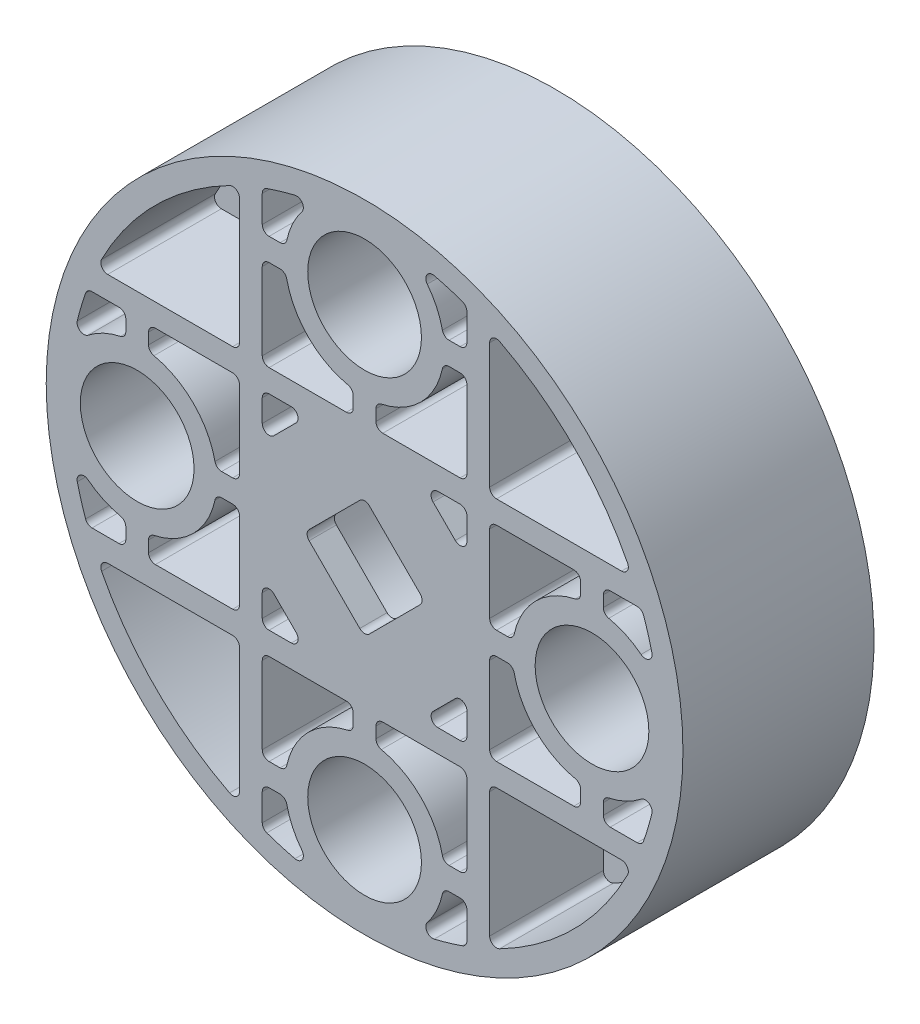
SolidWorks part; units mm, degrees
ref_plane "Front Plane" through (0, 0, 0) normal (0, 0, 1) x (1, 0, 0)
ref_plane "Top Plane" through (0, 0, 0) normal (0, 1, 0) x (1, 0, 0)
ref_plane "Right Plane" through (0, 0, 0) normal (1, 0, 0) x (0, 0, -1)
sketch "Sketch1" plane through (0, 0, 0) normal (0, 0, 1) x (1, 0, 0)
  line L0 (-22.0244, -11.2) -> (5.9756, -11.2) construction
  line L1 (-8.0244, -25.2) -> (-8.0244, 2.8) construction
  circle A0 centre (-8.0244, -11.2) radius 14 construction
  circle A1 centre (-8.0244, -11.2) radius 14
  circle A2 centre (-18.0244, -11.2) radius 2.5 construction
  circle A3 centre (-18.0244, -11.2) radius 2.5
  circle A4 centre (-8.0244, -1.2) radius 2.5 construction
  circle A5 centre (-8.0244, -1.2) radius 2.5
  circle A8 centre (-8.0244, -21.2) radius 2.5 construction
  circle A9 centre (1.9756, -11.2) radius 2.5 construction
  circle A10 centre (-8.0244, -21.2) radius 2.5
  circle A11 centre (1.9756, -11.2) radius 2.5
extrude "Boss-Extrude1" add sketch "Sketch1" along normal up to vertex (9.2 mm away)
sketch "Sketch2" plane through (0, 0, 9.2) normal (0, 0, 1) x (1, 0, 0)
  line L0 (-9.9744, -12.9197) -> (-9.9744, -9.4803)
  line L2 (-6.0744, -12.9197) -> (-6.0744, -9.4803)
  circle A0 centre (-8.0244, -11.2) radius 2.6
  dimension "D1" = 5.2
  dimension "D2" = 3.9
extrude "Cut-Extrude1" cut sketch "Sketch2" against normal through all contours L2 A0 L0
sketch "Sketch3" plane through (0, 0, 9.2) normal (0, 0, 1) x (1, 0, 0)
  line L0 (-12.5244, -23.2) -> (-12.5244, -23.3963)
  line L1 (-20.0244, -6.7) -> (-20.2207, -6.7)
  line L2 (-13.0244, 0.8) -> (-13.0244, -23.2) construction
  line L3 (-3.0244, -23.2) -> (-3.0244, 0.8) construction
  line L4 (-4.0744, -13.5574) -> (-4.0744, -8.8426)
  line L5 (-11.9744, -8.8426) -> (-11.9744, -13.5574)
  line L6 (-4.0744, -13.5574) -> (-4.0744, -8.8426)
  line L7 (-11.9744, -8.8426) -> (-11.9744, -13.5574)
  line L8 (-8.0244, -11.2) -> (-8.0244, 2.8) construction
  line L9 (-13.5244, 0.5792) -> (-13.5244, -22.9792)
  line L10 (-12.5244, 0.9963) -> (-12.5244, -23.2)
  line L11 (-2.5244, -22.9792) -> (-2.5244, 0.5792)
  line L12 (-3.5244, -23.3963) -> (-3.5244, 0.9963)
  line L13 (-3.5244, -23.2) -> (-3.5244, 0.8) construction
  line L14 (-2.5244, -23.2) -> (-2.5244, 0.8) construction
  line L15 (-12.5244, 0.8) -> (-12.5244, -23.2) construction
  line L16 (-13.5244, 0.8) -> (-13.5244, -23.2) construction
  line L17 (4.1719, -6.7) -> (-20.0244, -6.7)
  line L18 (3.7548, -5.7) -> (-19.8036, -5.7)
  line L19 (-20.2207, -15.7) -> (4.1719, -15.7)
  line L20 (-19.8036, -16.7) -> (3.7548, -16.7)
  line L21 (-8.0244, -11.2) -> (-12.5244, -23.2) construction
  line L22 (-8.0244, -11.2) -> (-20.0244, -6.7) construction
  circle A2 centre (-18.0244, -11.2) radius 3.5
  circle A3 centre (-18.0244, -11.2) radius 3.5
  circle A19 centre (-8.0244, -21.2) radius 3.5
  circle A20 centre (-8.0244, -21.2) radius 3.5
  circle A22 centre (1.9756, -11.2) radius 3.5
  circle A23 centre (1.9756, -11.2) radius 3.5
  circle A25 centre (-8.0244, -1.2) radius 3.5
  circle A26 centre (-8.0244, -1.2) radius 3.5
  circle A28 centre (-8.0244, -11.2) radius 13
  circle A29 centre (-8.0244, -11.2) radius 13
  arc A34 (-11.9744, -13.5574) -> (-4.0744, -13.5574) centre (-8.0244, -11.2) ccw
  arc A35 (-4.0744, -8.8426) -> (-11.9744, -8.8426) centre (-8.0244, -11.2) ccw
  arc A36 (-11.9744, -13.5574) -> (-4.0744, -13.5574) centre (-8.0244, -11.2) ccw
  arc A37 (-4.0744, -8.8426) -> (-11.9744, -8.8426) centre (-8.0244, -11.2) ccw
  dimension "D7" = 5
  dimension "D8" = 5
  dimension "D13" = 2
  dimension "D14" = 90
  dimension "D1" = 1
  dimension "D2" = 1
  dimension "D3" = 1
  dimension "D4" = 1
  dimension "D5" = 1
  dimension "D6" = 2
  dimension "D9" = 0.5
  dimension "D10" = 0.5
  dimension "D11" = 0.5
  dimension "D12" = 0.5
extrude "Cut-Extrude2" cut sketch "Sketch3" against normal blind 5 contours L9 A29 L18 | L12 A29 A26 L10 L18 | L1 A29 A3 L19 L9 L17 | A37 L17 L10 L19 A36 L7 | A37 L6 A36 L19 L12 L17 | A23 A29 L17 L11 L19 | L18 A29 L11 | L11 A29 L20 | L0 A29 A20 L12 L20 L10 | L20 A29 L9
sketch "Sketch4" plane through (0, 0, 0) normal (0, 0, -1) x (-1, 0, 0)
  circle A2 centre (8.0244, -11.2) radius 13
  circle A3 centre (8.0244, -11.2) radius 13
  dimension "D1" = 1
extrude "Cut-Extrude3" cut sketch "Sketch4" against normal blind 0.8
sketch "Sketch5" plane through (0, 0, 0.8) normal (0, 0, -1) x (-1, 0, 0)
  line L0 (8.0244, 2.8) -> (8.0244, -25.2) construction
  circle A0 centre (8.0244, -11.2) radius 4.25
  dimension "D1" = 8.5
extrude "Cut-Extrude4" cut sketch "Sketch5" against normal offset from surface (0.7 mm away) 1.5 up to face at (-21.0244, -11.2, 0)
sketch "Sketch6" plane through (0, 0, 0.8) normal (0, 0, -1) x (-1, 0, 0)
  circle A0 centre (8.0244, -11.2) radius 4.25 construction
  circle A1 centre (8.0244, -11.2) radius 4.25
  circle A2 centre (8.0244, -11.2) radius 5.25
  dimension "D1" = 1
extrude "Boss-Extrude2" add sketch "Sketch6" along normal up to surface (0.8 mm away) up to face at (-21.0244, -11.2, 0)
sketch "Sketch7" plane through (0, 0, 0.8) normal (0, 0, -1) x (-1, 0, 0)
  line L0 (7.0705, -15.7) -> (3.5244, -15.7) construction
  line L1 (3.5244, -6.7) -> (7.0705, -6.7) construction
  line L2 (3.5244, -5.7) -> (12.5244, -5.7) construction
  line L3 (12.5244, -16.7) -> (3.5244, -16.7) construction
  line L4 (-3.7548, -5.7) -> (2.5244, -5.7) construction
  line L5 (-4.1719, -6.7) -> (2.5244, -6.7) construction
  line L6 (2.5244, -15.7) -> (-4.1719, -15.7) construction
  line L7 (2.5244, -16.7) -> (-3.7548, -16.7) construction
  line L8 (2.5244, -22.9792) -> (2.5244, -16.7) construction
  line L9 (3.5244, -23.3963) -> (3.5244, -16.7) construction
  line L10 (2.5244, -15.7) -> (2.5244, -6.7) construction
  line L11 (2.5244, -5.7) -> (2.5244, 0.5792) construction
  line L12 (3.5244, -5.7) -> (3.5244, 0.9963) construction
  line L13 (3.5244, -15.7) -> (3.5244, -6.7) construction
  line L14 (12.5244, -16.7) -> (12.5244, -23.3963) construction
  line L15 (12.5244, 0.9963) -> (12.5244, -5.7) construction
  line L16 (12.5244, -6.7) -> (12.5244, -15.7) construction
  line L17 (13.5244, -16.7) -> (13.5244, -22.9792) construction
  line L18 (13.5244, 0.5792) -> (13.5244, -5.7) construction
  line L19 (13.5244, -5.7) -> (19.8036, -5.7) construction
  line L20 (13.5244, -6.7) -> (20.2207, -6.7) construction
  line L21 (13.5244, -6.7) -> (13.5244, -15.7) construction
  line L22 (20.2207, -15.7) -> (13.5244, -15.7) construction
  line L23 (19.8036, -16.7) -> (13.5244, -16.7) construction
  line L24 (12.5244, -15.7) -> (3.5244, -15.7)
  line L25 (3.5244, -6.7) -> (12.5244, -6.7)
  line L26 (3.5244, -5.7) -> (12.5244, -5.7)
  line L27 (12.5244, -16.7) -> (3.5244, -16.7)
  line L28 (-3.7548, -5.7) -> (2.5244, -5.7)
  line L29 (-4.1719, -6.7) -> (2.5244, -6.7)
  line L30 (2.5244, -15.7) -> (-4.1719, -15.7)
  line L31 (2.5244, -16.7) -> (-3.7548, -16.7)
  line L32 (2.5244, -22.9792) -> (2.5244, -16.7)
  line L33 (3.5244, -23.3963) -> (3.5244, -16.7)
  line L34 (2.5244, -15.7) -> (2.5244, -6.7)
  line L35 (2.5244, -5.7) -> (2.5244, 0.5792)
  line L36 (3.5244, -5.7) -> (3.5244, 0.9963)
  line L37 (3.5244, -15.7) -> (3.5244, -6.7)
  line L38 (12.5244, -16.7) -> (12.5244, -23.3963)
  line L39 (12.5244, 0.9963) -> (12.5244, -5.7)
  line L40 (12.5244, -6.7) -> (12.5244, -15.7)
  line L41 (13.5244, -16.7) -> (13.5244, -22.9792)
  line L42 (13.5244, 0.5792) -> (13.5244, -5.7)
  line L43 (13.5244, -5.7) -> (19.8036, -5.7)
  line L44 (13.5244, -6.7) -> (20.2207, -6.7)
  line L45 (13.5244, -6.7) -> (13.5244, -15.7)
  line L46 (20.2207, -15.7) -> (13.5244, -15.7)
  line L47 (19.8036, -16.7) -> (13.5244, -16.7)
  circle A2 centre (18.0244, -11.2) radius 3.5
  circle A3 centre (18.0244, -11.2) radius 3.5
  circle A5 centre (8.0244, -1.2) radius 3.5
  circle A6 centre (8.0244, -1.2) radius 3.5
  circle A8 centre (-1.9756, -11.2) radius 3.5
  circle A9 centre (-1.9756, -11.2) radius 3.5
  circle A10 centre (8.0244, -11.2) radius 13 construction
  circle A11 centre (8.0244, -21.2) radius 3.5
  circle A12 centre (8.0244, -21.2) radius 3.5
  circle A13 centre (8.0244, -11.2) radius 13
  circle A14 centre (8.0244, -11.2) radius 5.25 construction
  circle A15 centre (8.0244, -11.2) radius 5.25
  circle A17 centre (8.0244, -11.2) radius 14
  circle A18 centre (8.0244, -11.2) radius 14
  circle M6 centre (8.0244, -11.2) radius 13
  circle M11 centre (8.0244, -11.2) radius 5.25
  dimension "D1" = 1
  dimension "D2" = 1
  dimension "D3" = 1
  dimension "D4" = 1
  dimension "D5" = 0
extrude "Cut-Extrude5" cut sketch "Sketch7" against normal offset from surface (2.4 mm away) 1 contours L28 L35 M6 | A9 L30 L34 L29 M6 | L32 L31 M6 | A12 L38 L27 L33 M6 | A6 L36 L26 L39 M6 | L42 L43 M6 | A3 L44 L45 L46 M6 | L47 L41 M6 | L40 L24 M11 | L40 L25 M11 | L37 L25 M11 | L37 L24 M11 up to face at (-0.2471, -18.9773, 4.2)
chamfer "Chamfer1" distance 0.6 angle 45 4 edges at (-6.0744, -11.2, 1.5) (-8.0244, -8.6, 1.5) (-8.0244, -13.8, 1.5) (-9.9744, -11.2, 1.5)
sketch "Sketch8" plane through (0, 0, 9.2) normal (0, 0, 1) x (1, 0, 0)
  line L0 (-11.9744, -8.8426) -> (-11.9744, -13.5574) construction
  line L1 (-11.9744, -8.8426) -> (-11.9744, -13.5574)
  line L2 (-4.0744, -13.5574) -> (-4.0744, -8.8426) construction
  line L3 (-4.0744, -13.5574) -> (-4.0744, -8.8426)
  line L4 (-8.0244, -7.1341) -> (-12.0903, -11.2)
  line L5 (-3.9586, -11.2) -> (-8.0244, -7.1341)
  line L6 (-8.0244, -15.2659) -> (-3.9586, -11.2)
  line L7 (-12.0903, -11.2) -> (-8.0244, -15.2659)
  line L8 (-8.0244, -7.1341) -> (-12.0903, -11.2)
  line L9 (-3.9586, -11.2) -> (-8.0244, -7.1341)
  line L10 (-8.0244, -15.2659) -> (-3.9586, -11.2)
  line L11 (-12.0903, -11.2) -> (-8.0244, -15.2659)
  line L12 (-8.0244, -13.8517) -> (-5.3728, -11.2)
  line L13 (-10.6761, -11.2) -> (-8.0244, -13.8517)
  line L14 (-8.0244, -8.5483) -> (-10.6761, -11.2)
  line L15 (-5.3728, -11.2) -> (-8.0244, -8.5483)
  line L16 (-8.0244, -13.8517) -> (-5.3728, -11.2)
  line L17 (-10.6761, -11.2) -> (-8.0244, -13.8517)
  line L18 (-8.0244, -8.5483) -> (-10.6761, -11.2)
  line L19 (-5.3728, -11.2) -> (-8.0244, -8.5483)
  line L20 (-3.5244, -6.7) -> (-12.5244, -6.7)
  line L21 (-3.5244, -15.7) -> (-3.5244, -6.7)
  line L22 (-12.5244, -15.7) -> (-3.5244, -15.7)
  line L23 (-12.5244, -6.7) -> (-12.5244, -15.7)
  line L24 (-3.5244, -6.7) -> (-12.5244, -6.7)
  line L25 (-3.5244, -15.7) -> (-3.5244, -6.7)
  line L26 (-12.5244, -15.7) -> (-3.5244, -15.7)
  line L27 (-12.5244, -6.7) -> (-12.5244, -15.7)
  dimension "D1" = 0
  dimension "D2" = 0
  dimension "D3" = 0
extrude "Cut-Extrude6" cut sketch "Sketch8" against normal up to surface (5 mm away)
sketch "Sketch9" plane through (0, 0, 9.2) normal (0, 0, 1) x (1, 0, 0)
  line L0 (-4.0744, -13.5574) -> (-4.0744, -8.8426) construction
  line L1 (-11.9744, -8.8426) -> (-11.9744, -13.5574) construction
  line L2 (-4.0744, -13.5574) -> (-4.0744, -8.8426)
  line L3 (-11.9744, -8.8426) -> (-11.9744, -13.5574)
  line L4 (-3.5244, -6.7) -> (-12.5244, -6.7)
  line L5 (-12.5244, -6.7) -> (-12.5244, -15.7)
  line L6 (-12.5244, -15.7) -> (-3.5244, -15.7)
  line L7 (-3.5244, -15.7) -> (-3.5244, -6.7)
  line L8 (-3.5244, -6.7) -> (-12.5244, -6.7)
  line L9 (-12.5244, -6.7) -> (-12.5244, -15.7)
  line L10 (-12.5244, -15.7) -> (-3.5244, -15.7)
  line L11 (-3.5244, -15.7) -> (-3.5244, -6.7)
  line L12 (-8.0244, -13.8517) -> (-5.3728, -11.2)
  line L13 (-5.3728, -11.2) -> (-8.0244, -8.5483)
  line L14 (-8.0244, -8.5483) -> (-10.6761, -11.2)
  line L15 (-10.6761, -11.2) -> (-8.0244, -13.8517)
  line L16 (-8.0244, -13.8517) -> (-5.3728, -11.2)
  line L17 (-5.3728, -11.2) -> (-8.0244, -8.5483)
  line L18 (-8.0244, -8.5483) -> (-10.6761, -11.2)
  line L19 (-10.6761, -11.2) -> (-8.0244, -13.8517)
  line L20 (-8.0244, -7.1341) -> (-12.0903, -11.2)
  line L21 (-12.0903, -11.2) -> (-8.0244, -15.2659)
  line L22 (-8.0244, -15.2659) -> (-3.9586, -11.2)
  line L23 (-3.9586, -11.2) -> (-8.0244, -7.1341)
  line L24 (-8.0244, -7.1341) -> (-12.0903, -11.2)
  line L25 (-12.0903, -11.2) -> (-8.0244, -15.2659)
  line L26 (-8.0244, -15.2659) -> (-3.9586, -11.2)
  line L27 (-3.9586, -11.2) -> (-8.0244, -7.1341)
  line M18 (-11.9744, -11.0841) -> (-11.9744, -11.3159)
  line M21 (-4.0744, -11.3159) -> (-4.0744, -11.0841)
  dimension "D1" = 0
  dimension "D2" = 0
  dimension "D3" = 0
extrude "Boss-Extrude3" add sketch "Sketch9" against normal up to surface (5 mm away) contours L24 L25 M18 | L26 L27 M21 up to face at (-8.0244, -11.2, 4.2)
sketch "Sketch10" plane through (0, 0, 9.2) normal (0, 0, 1) x (1, 0, 0)
  line L4 (-8.0244, -7.1341) -> (-12.0903, -11.2)
  line L5 (-12.0903, -11.2) -> (-8.0244, -15.2659)
  line L6 (-8.0244, -15.2659) -> (-3.9586, -11.2)
  line L7 (-3.9586, -11.2) -> (-8.0244, -7.1341)
  line L8 (-8.0244, -7.1341) -> (-12.0903, -11.2)
  line L9 (-12.0903, -11.2) -> (-8.0244, -15.2659)
  line L10 (-8.0244, -15.2659) -> (-3.9586, -11.2)
  line L11 (-3.9586, -11.2) -> (-8.0244, -7.1341)
  dimension "D1" = 0
extrude "Boss-Extrude4" add sketch "Sketch10" against normal up to surface (0.2 mm away)
sketch "Sketch11" plane through (0, 0, 9.2) normal (0, 0, 1) x (1, 0, 0)
  line L0 (-11.9744, -8.8426) -> (-11.9744, -13.5574) construction
  line L1 (-4.0744, -13.5574) -> (-4.0744, -8.8426) construction
  line L2 (-11.9744, -8.8426) -> (-11.9744, -13.5574)
  line L3 (-4.0744, -13.5574) -> (-4.0744, -8.8426)
  line L4 (-8.0244, -7.1341) -> (-12.0903, -11.2)
  line L5 (-12.0903, -11.2) -> (-8.0244, -15.2659)
  line L6 (-8.0244, -15.2659) -> (-3.9586, -11.2)
  line L7 (-3.9586, -11.2) -> (-8.0244, -7.1341)
  line L8 (-8.0244, -7.1341) -> (-12.0903, -11.2)
  line L9 (-12.0903, -11.2) -> (-8.0244, -15.2659)
  line L10 (-8.0244, -15.2659) -> (-3.9586, -11.2)
  line L11 (-3.9586, -11.2) -> (-8.0244, -7.1341)
  line L12 (-8.0244, -13.8517) -> (-5.3728, -11.2)
  line L13 (-5.3728, -11.2) -> (-8.0244, -8.5483)
  line L14 (-8.0244, -8.5483) -> (-10.6761, -11.2)
  line L15 (-10.6761, -11.2) -> (-8.0244, -13.8517)
  line L16 (-8.0244, -13.8517) -> (-5.3728, -11.2)
  line L17 (-5.3728, -11.2) -> (-8.0244, -8.5483)
  line L18 (-8.0244, -8.5483) -> (-10.6761, -11.2)
  line L19 (-10.6761, -11.2) -> (-8.0244, -13.8517)
  line L20 (-3.5244, -6.7) -> (-12.5244, -6.7)
  line L21 (-12.5244, -6.7) -> (-12.5244, -15.7)
  line L22 (-12.5244, -15.7) -> (-3.5244, -15.7)
  line L23 (-3.5244, -15.7) -> (-3.5244, -6.7)
  line L24 (-3.5244, -6.7) -> (-12.5244, -6.7)
  line L25 (-12.5244, -6.7) -> (-12.5244, -15.7)
  line L26 (-12.5244, -15.7) -> (-3.5244, -15.7)
  line L27 (-3.5244, -15.7) -> (-3.5244, -6.7)
  dimension "D1" = 0
  dimension "D2" = 0
  dimension "D3" = 0
extrude "Cut-Extrude7" cut sketch "Sketch11" against normal up to surface (0.2 mm away) contours L18 L19 L16 L17 up to face at (-8.0244, -11.2, 9)
fillet "Fillet1" [suppressed] radius 0.2
sketch "Sketch12" plane through (0, 0, 9.2) normal (0, 0, 1) x (1, 0, 0)
  line L4 (-12.0903, -11.2) -> (-8.0244, -15.2659)
  line L5 (-8.0244, -7.1341) -> (-12.0903, -11.2)
  line L6 (-3.9586, -11.2) -> (-8.0244, -7.1341)
  line L7 (-8.0244, -15.2659) -> (-3.9586, -11.2)
  line L8 (-12.0903, -11.2) -> (-8.0244, -15.2659)
  line L9 (-8.0244, -7.1341) -> (-12.0903, -11.2)
  line L10 (-3.9586, -11.2) -> (-8.0244, -7.1341)
  line L11 (-8.0244, -15.2659) -> (-3.9586, -11.2)
  line L12 (-13.1509, -11.2) -> (-8.0244, -16.3265)
  line L13 (-8.0244, -6.0735) -> (-13.1509, -11.2)
  line L14 (-2.8979, -11.2) -> (-8.0244, -6.0735)
  line L15 (-8.0244, -16.3265) -> (-2.8979, -11.2)
  line L16 (-13.1509, -11.2) -> (-8.0244, -16.3265)
  line L17 (-8.0244, -6.0735) -> (-13.1509, -11.2)
  line L18 (-2.8979, -11.2) -> (-8.0244, -6.0735)
  line L19 (-8.0244, -16.3265) -> (-2.8979, -11.2)
  dimension "D1" = 0
  dimension "D2" = 0
extrude "Boss-Extrude5" [suppressed] add sketch "Sketch12" against normal up to surface (5 mm away)
sketch "Sketch13" plane through (0, 0, 9.2) normal (0, 0, 1) x (1, 0, 0)
  line L0 (-20.2207, -15.7) -> (-13.5244, -15.7) construction
  line L1 (-13.5244, -6.7) -> (-13.5244, -15.7) construction
  line L2 (-13.5244, -6.7) -> (-20.2207, -6.7) construction
  line L3 (-12.5244, 0.9963) -> (-12.5244, -5.7) construction
  line L4 (-3.5244, -5.7) -> (-12.5244, -5.7) construction
  line L5 (-3.5244, -5.7) -> (-3.5244, 0.9963) construction
  line L6 (-3.5244, -1.7) -> (-12.5244, -1.7) construction
  line L7 (-8.5244, -1.2) -> (-8.5244, -21.2) construction
  line L8 (-7.5244, -1.2) -> (-7.5244, -21.2) construction
  line L9 (-3.5244, -0.7) -> (-12.5244, -0.7) construction
  line L10 (-3.5244, -20.7) -> (-12.5244, -20.7) construction
  line L11 (-3.5244, -21.7) -> (-12.5244, -21.7) construction
  line L12 (-3.5244, -16.7) -> (-3.5244, -23.3963) construction
  line L13 (-12.5244, -16.7) -> (-3.5244, -16.7) construction
  line L14 (-12.5244, -23.3963) -> (-12.5244, -16.7) construction
  line L15 (-2.5244, -6.7) -> (4.1719, -6.7) construction
  line L16 (-2.5244, -15.7) -> (-2.5244, -6.7) construction
  line L17 (-18.0244, -11.7) -> (1.9756, -11.7) construction
  line L18 (-18.0244, -10.7) -> (1.9756, -10.7) construction
  line L19 (1.4756, -6.7) -> (1.4756, -15.7) construction
  line L20 (2.4756, -6.7) -> (2.4756, -15.7) construction
  line L21 (4.1719, -15.7) -> (-2.5244, -15.7) construction
  line L22 (-18.5244, -6.7) -> (-18.5244, -15.7) construction
  line L23 (-17.5244, -6.7) -> (-17.5244, -15.7) construction
  line L24 (-20.2207, -15.7) -> (-13.5244, -15.7)
  line L25 (-13.5244, -6.7) -> (-13.5244, -15.7)
  line L26 (-13.5244, -6.7) -> (-20.2207, -6.7)
  line L27 (-12.5244, 0.9963) -> (-12.5244, -5.7)
  line L28 (-3.5244, -5.7) -> (-12.5244, -5.7)
  line L29 (-3.5244, -5.7) -> (-3.5244, 0.9963)
  line L30 (-3.5244, -1.7) -> (-12.5244, -1.7)
  line L31 (-8.5244, -1.2) -> (-8.5244, -21.2)
  line L32 (-7.5244, -1.2) -> (-7.5244, -21.2)
  line L33 (-3.5244, -0.7) -> (-12.5244, -0.7)
  line L34 (-3.5244, -20.7) -> (-12.5244, -20.7)
  line L35 (-3.5244, -21.7) -> (-12.5244, -21.7)
  line L36 (-3.5244, -16.7) -> (-3.5244, -23.3963)
  line L37 (-12.5244, -16.7) -> (-3.5244, -16.7)
  line L38 (-12.5244, -23.3963) -> (-12.5244, -16.7)
  line L39 (-2.5244, -6.7) -> (4.1719, -6.7)
  line L40 (-2.5244, -15.7) -> (-2.5244, -6.7)
  line L41 (-18.0244, -11.7) -> (1.9756, -11.7)
  line L42 (-18.0244, -10.7) -> (1.9756, -10.7)
  line L43 (1.4756, -6.7) -> (1.4756, -15.7)
  line L44 (2.4756, -6.7) -> (2.4756, -15.7)
  line L45 (4.1719, -15.7) -> (-2.5244, -15.7)
  line L46 (-18.5244, -6.7) -> (-18.5244, -15.7)
  line L47 (-17.5244, -6.7) -> (-17.5244, -15.7)
  line L48 (-12.5244, -6.7) -> (-12.5244, -15.7) construction
  line L49 (-3.5244, -15.7) -> (-3.5244, -6.7) construction
  line L50 (-8.0244, -15.2659) -> (-3.9586, -11.2) construction
  line L51 (-8.0244, -15.2659) -> (-12.0903, -11.2) construction
  line L52 (-12.0903, -11.2) -> (-8.0244, -7.1341) construction
  line L53 (-8.0244, -7.1341) -> (-3.9586, -11.2) construction
  line L54 (-12.5244, -6.7) -> (-12.5244, -15.7)
  line L55 (-3.5244, -15.7) -> (-3.5244, -6.7)
  line L56 (-8.0244, -15.2659) -> (-3.9586, -11.2)
  line L57 (-8.0244, -15.2659) -> (-12.0903, -11.2)
  line L58 (-12.0903, -11.2) -> (-8.0244, -7.1341)
  line L59 (-8.0244, -7.1341) -> (-3.9586, -11.2)
  arc A0 (-5.9754, -24.0375) -> (-10.0735, -24.0375) centre (-8.0244, -21.2) ccw construction
  arc A1 (4.8131, -9.151) -> (4.8131, -13.249) centre (1.9756, -11.2) ccw construction
  arc A2 (-20.8619, -13.249) -> (-20.8619, -9.151) centre (-18.0244, -11.2) ccw construction
  arc A3 (-10.0735, 1.6375) -> (-5.9754, 1.6375) centre (-8.0244, -1.2) ccw construction
  arc A4 (-5.9754, -24.0375) -> (-10.0735, -24.0375) centre (-8.0244, -21.2) ccw
  arc A5 (4.8131, -9.151) -> (4.8131, -13.249) centre (1.9756, -11.2) ccw
  arc A6 (-20.8619, -13.249) -> (-20.8619, -9.151) centre (-18.0244, -11.2) ccw
  arc A7 (-10.0735, 1.6375) -> (-5.9754, 1.6375) centre (-8.0244, -1.2) ccw
  line M61 (-12.5244, -6.7) -> (-3.5244, -6.7)
  line M62 (-3.5244, -6.7) -> (-3.5244, -15.7)
  line M63 (-3.5244, -15.7) -> (-12.5244, -15.7)
  line M64 (-12.5244, -15.7) -> (-12.5244, -6.7)
extrude "Boss-Extrude6" add sketch "Sketch13" against normal up to surface (5 mm away) contours A4 L34 L38 L35 | A4 L32 L37 L31 | A4 L35 L36 L34 | A5 L43 L45 L44 | A5 L42 L40 L41 | A5 L44 L39 L43 | A7 L30 L29 L33 | A7 L31 L28 L32 | A7 L33 L27 L30 | A6 L41 L25 L42 | A6 L47 L26 L46 | A6 L46 L24 L47 | L57 L58 L42 L41 M64 | L42 L59 L56 L41 M62 | L56 L57 L31 L32 M63 | L58 L59 L32 L31 M61 up to face at (-8.0244, -20.3416, 4.2)
sketch "Sketch14" plane through (0, 0, 0.8) normal (0, 0, -1) x (-1, 0, 0)
  circle A0 centre (8.0244, -11.2) radius 18.4031
extrude "Cut-Extrude8" cut sketch "Sketch14" along normal blind 14
sketch "Sketch15" plane through (0, 0, 0.8) normal (0, 0, -1) x (-1, 0, 0)
  line L1 (3.5244, -6.7) -> (12.5244, -6.7)
  line L2 (3.5244, -6.7) -> (3.5244, -15.7)
  line L3 (3.5244, -15.7) -> (12.5244, -15.7)
  line L4 (12.5244, -6.7) -> (12.5244, -15.7)
extrude "Cut-Extrude9" cut sketch "Sketch15" against normal up to surface (2.4 mm away) up to face at (1.1172, -11.2, 3.2)
sketch "Sketch18" plane through (0, 0, 9.2) normal (0, 0, 1) x (1, 0, 0)
  line L5 (-8.0244, -8.5483) -> (-10.6761, -11.2)
  line L6 (-5.3728, -11.2) -> (-8.0244, -8.5483)
  line L7 (-8.0244, -13.8517) -> (-5.3728, -11.2)
  line L8 (-10.6761, -11.2) -> (-8.0244, -13.8517)
  line L9 (-8.0244, -8.5483) -> (-10.6761, -11.2)
  line L10 (-5.3728, -11.2) -> (-8.0244, -8.5483)
  line L11 (-8.0244, -13.8517) -> (-5.3728, -11.2)
  line L12 (-10.6761, -11.2) -> (-8.0244, -13.8517)
  dimension "D1" = 0
extrude "Cut-Extrude10" cut sketch "Sketch18" against normal through all
sketch "Sketch19" plane through (0, 0, 3.2) normal (0, 0, -1) x (-1, 0, 0)
  line L1 (9.9744, -10.4983) -> (8.0766, -8.6005) construction
  line L2 (6.0744, -10.4983) -> (7.9722, -8.6005)
  line L3 (6.0744, -9.4803) -> (6.0744, -10.4983)
  line L4 (6.0744, -10.4983) -> (7.9722, -8.6005)
  line L5 (6.0744, -9.4803) -> (6.0744, -10.4983)
  line L6 (8.0766, -13.7995) -> (9.9744, -11.9017) construction
  line L7 (7.9722, -13.7995) -> (6.0744, -11.9017)
  line L8 (6.0744, -11.9017) -> (6.0744, -12.9197)
  line L9 (7.9722, -13.7995) -> (6.0744, -11.9017)
  line L10 (6.0744, -11.9017) -> (6.0744, -12.9197)
  line L11 (9.9744, -10.4983) -> (8.0766, -8.6005)
  line L12 (8.0766, -13.7995) -> (9.9744, -11.9017)
  line L16 (10.6761, -11.2) -> (9.9744, -10.4983)
  line L17 (9.9744, -11.9017) -> (10.6761, -11.2)
  line L18 (9.9744, -12.9197) -> (9.9744, -11.9017)
  line L19 (8.0244, -13.8517) -> (8.0766, -13.7995)
  line L20 (7.9722, -13.7995) -> (8.0244, -13.8517)
  line L21 (6.0744, -11.9017) -> (6.0744, -12.9197)
  line L22 (5.3728, -11.2) -> (6.0744, -11.9017)
  line L23 (6.0744, -10.4983) -> (5.3728, -11.2)
  line L24 (6.0744, -9.4803) -> (6.0744, -10.4983)
  line L25 (8.0244, -8.5483) -> (7.9722, -8.6005)
  line L26 (8.0766, -8.6005) -> (8.0244, -8.5483)
  line L27 (9.9744, -10.4983) -> (9.9744, -9.4803)
  line L28 (10.6761, -11.2) -> (9.9744, -10.4983)
  line L29 (9.9744, -11.9017) -> (10.6761, -11.2)
  line L30 (9.9744, -12.9197) -> (9.9744, -11.9017)
  line L31 (8.0244, -13.8517) -> (8.0766, -13.7995)
  line L32 (7.9722, -13.7995) -> (8.0244, -13.8517)
  line L33 (6.0744, -11.9017) -> (6.0744, -12.9197)
  line L34 (5.3728, -11.2) -> (6.0744, -11.9017)
  line L35 (6.0744, -10.4983) -> (5.3728, -11.2)
  line L36 (6.0744, -9.4803) -> (6.0744, -10.4983)
  line L37 (8.0244, -8.5483) -> (7.9722, -8.6005)
  line L38 (8.0766, -8.6005) -> (8.0244, -8.5483)
  line L39 (9.9744, -10.4983) -> (9.9744, -9.4803)
  arc A1 (7.9722, -8.6005) -> (6.0744, -9.4803) centre (8.0244, -11.2) ccw
  arc A2 (7.9722, -8.6005) -> (6.0744, -9.4803) centre (8.0244, -11.2) ccw
  arc A4 (6.0744, -12.9197) -> (7.9722, -13.7995) centre (8.0244, -11.2) ccw
  arc A5 (6.0744, -12.9197) -> (7.9722, -13.7995) centre (8.0244, -11.2) ccw
  arc A7 (8.0766, -13.7995) -> (9.9744, -12.9197) centre (8.0244, -11.2) ccw
  arc A8 (6.0744, -12.9197) -> (7.9722, -13.7995) centre (8.0244, -11.2) ccw
  arc A9 (7.9722, -8.6005) -> (6.0744, -9.4803) centre (8.0244, -11.2) ccw
  arc A10 (9.9744, -9.4803) -> (8.0766, -8.6005) centre (8.0244, -11.2) ccw
  arc A11 (8.0766, -13.7995) -> (9.9744, -12.9197) centre (8.0244, -11.2) ccw
  arc A12 (6.0744, -12.9197) -> (7.9722, -13.7995) centre (8.0244, -11.2) ccw
  arc A13 (7.9722, -8.6005) -> (6.0744, -9.4803) centre (8.0244, -11.2) ccw
  arc A14 (9.9744, -9.4803) -> (8.0766, -8.6005) centre (8.0244, -11.2) ccw
  line M29 (9.9744, -11.9017) -> (9.9744, -12.9197)
  arc M30 (9.9744, -12.9197) -> (8.0766, -13.7995) centre (8.0244, -11.2) cw
  arc M33 (7.9722, -13.7995) -> (6.0744, -12.9197) centre (8.0244, -11.2) cw
  line M34 (6.0744, -12.9197) -> (6.0744, -11.9017)
  line M37 (6.0744, -10.4983) -> (6.0744, -9.4803)
  arc M38 (6.0744, -9.4803) -> (7.9722, -8.6005) centre (8.0244, -11.2) cw
  arc M41 (8.0766, -8.6005) -> (9.9744, -9.4803) centre (8.0244, -11.2) cw
  line M42 (9.9744, -9.4803) -> (9.9744, -10.4983)
  dimension "D1" = 0
  dimension "D2" = 0
  dimension "D3" = 0
extrude "Boss-Extrude7" add sketch "Sketch19" against normal up to surface (5.8 mm away) contours L4 M37 M38 | L11 M42 M41 | L9 M33 M34 | L12 M30 M29 up to face at (-6.6762, -12.94, 9)
sketch "Sketch20" plane through (0, 0, 3.2) normal (0, 0, -1) x (-1, 0, 0)
  line L0 (3.5244, -15.7) -> (3.5244, -6.7) construction
  line L1 (12.5244, -6.7) -> (12.5244, -15.7) construction
  line L2 (8.5244, -1.2) -> (8.5244, -21.2) construction
  line L3 (3.5244, -1.7) -> (12.5244, -1.7) construction
  line L4 (12.0903, -11.2) -> (8.0244, -7.1341)
  line L5 (8.0244, -7.1341) -> (3.9586, -11.2)
  line L6 (3.9586, -11.2) -> (8.0244, -15.2659)
  line L7 (8.0244, -15.2659) -> (12.0903, -11.2)
  line L8 (12.0903, -11.2) -> (8.0244, -7.1341)
  line L9 (8.0244, -7.1341) -> (3.9586, -11.2)
  line L10 (3.9586, -11.2) -> (8.0244, -15.2659)
  line L11 (8.0244, -15.2659) -> (12.0903, -11.2)
  line L12 (12.5244, 0.9963) -> (12.5244, -5.7) construction
  line L13 (3.5244, -5.7) -> (12.5244, -5.7) construction
  line L14 (3.5244, -5.7) -> (3.5244, 0.9963) construction
  line L15 (20.2207, -15.7) -> (13.5244, -15.7) construction
  line L16 (13.5244, -6.7) -> (13.5244, -15.7) construction
  line L17 (13.5244, -6.7) -> (20.2207, -6.7) construction
  line L18 (3.5244, -16.7) -> (3.5244, -23.3963) construction
  line L19 (12.5244, -16.7) -> (3.5244, -16.7) construction
  line L20 (12.5244, -23.3963) -> (12.5244, -16.7) construction
  line L21 (3.5244, -21.7) -> (12.5244, -21.7) construction
  line L22 (3.5244, -20.7) -> (12.5244, -20.7) construction
  line L23 (3.5244, -0.7) -> (12.5244, -0.7) construction
  line L24 (7.5244, -1.2) -> (7.5244, -21.2) construction
  line L25 (18.0244, -11.7) -> (-1.9756, -11.7) construction
  line L26 (2.5244, -6.7) -> (-4.1719, -6.7) construction
  line L27 (2.5244, -15.7) -> (2.5244, -6.7) construction
  line L28 (-4.1719, -15.7) -> (2.5244, -15.7) construction
  line L29 (17.5244, -6.7) -> (17.5244, -15.7) construction
  line L30 (18.5244, -6.7) -> (18.5244, -15.7) construction
  line L31 (-2.4756, -6.7) -> (-2.4756, -15.7) construction
  line L32 (-1.4756, -6.7) -> (-1.4756, -15.7) construction
  line L33 (18.0244, -10.7) -> (-1.9756, -10.7) construction
  line L34 (3.5244, -15.7) -> (3.5244, -6.7)
  line L35 (12.5244, -6.7) -> (12.5244, -15.7)
  line L36 (8.5244, -1.2) -> (8.5244, -21.2)
  line L37 (3.5244, -1.7) -> (12.5244, -1.7)
  line L38 (12.5244, 0.9963) -> (12.5244, -5.7)
  line L39 (3.5244, -5.7) -> (12.5244, -5.7)
  line L40 (3.5244, -5.7) -> (3.5244, 0.9963)
  line L41 (20.2207, -15.7) -> (13.5244, -15.7)
  line L42 (13.5244, -6.7) -> (13.5244, -15.7)
  line L43 (13.5244, -6.7) -> (20.2207, -6.7)
  line L44 (3.5244, -16.7) -> (3.5244, -23.3963)
  line L45 (12.5244, -16.7) -> (3.5244, -16.7)
  line L46 (12.5244, -23.3963) -> (12.5244, -16.7)
  line L47 (3.5244, -21.7) -> (12.5244, -21.7)
  line L48 (3.5244, -20.7) -> (12.5244, -20.7)
  line L49 (3.5244, -0.7) -> (12.5244, -0.7)
  line L50 (7.5244, -1.2) -> (7.5244, -21.2)
  line L51 (18.0244, -11.7) -> (-1.9756, -11.7)
  line L52 (2.5244, -6.7) -> (-4.1719, -6.7)
  line L53 (2.5244, -15.7) -> (2.5244, -6.7)
  line L54 (-4.1719, -15.7) -> (2.5244, -15.7)
  line L55 (17.5244, -6.7) -> (17.5244, -15.7)
  line L56 (18.5244, -6.7) -> (18.5244, -15.7)
  line L57 (-2.4756, -6.7) -> (-2.4756, -15.7)
  line L58 (-1.4756, -6.7) -> (-1.4756, -15.7)
  line L59 (18.0244, -10.7) -> (-1.9756, -10.7)
  line L64 (10.6761, -11.2) -> (8.0244, -8.5483)
  line L65 (8.0244, -13.8517) -> (10.6761, -11.2)
  line L66 (5.3728, -11.2) -> (8.0244, -13.8517)
  line L67 (8.0244, -8.5483) -> (5.3728, -11.2)
  line L68 (10.6761, -11.2) -> (8.0244, -8.5483)
  line L69 (8.0244, -13.8517) -> (10.6761, -11.2)
  line L70 (5.3728, -11.2) -> (8.0244, -13.8517)
  line L71 (8.0244, -8.5483) -> (5.3728, -11.2)
  arc A0 (10.0735, -24.0375) -> (5.9754, -24.0375) centre (8.0244, -21.2) ccw construction
  arc A1 (5.9754, 1.6375) -> (10.0735, 1.6375) centre (8.0244, -1.2) ccw construction
  arc A2 (20.8619, -9.151) -> (20.8619, -13.249) centre (18.0244, -11.2) ccw construction
  arc A3 (-4.8131, -13.249) -> (-4.8131, -9.151) centre (-1.9756, -11.2) ccw construction
  arc A4 (10.0735, -24.0375) -> (5.9754, -24.0375) centre (8.0244, -21.2) ccw
  arc A5 (5.9754, 1.6375) -> (10.0735, 1.6375) centre (8.0244, -1.2) ccw
  arc A6 (20.8619, -9.151) -> (20.8619, -13.249) centre (18.0244, -11.2) ccw
  arc A7 (-4.8131, -13.249) -> (-4.8131, -9.151) centre (-1.9756, -11.2) ccw
  line M9 (8.0244, -8.5483) -> (10.6761, -11.2)
  line M10 (10.6761, -11.2) -> (8.0244, -13.8517)
  line M11 (8.0244, -13.8517) -> (5.3728, -11.2)
  line M12 (5.3728, -11.2) -> (8.0244, -8.5483)
  line M14 (12.5244, -6.7) -> (3.5244, -6.7)
  line M16 (3.5244, -15.7) -> (12.5244, -15.7)
  dimension "D1" = 0
  dimension "D2" = 0
extrude "Boss-Extrude8" add sketch "Sketch20" along normal up to surface (2.4 mm away) contours A7 L58 L52 L57 | A7 L57 L54 L58 | A7 L51 L53 L59 | L9 L59 L34 L51 L10 | L59 L9 L10 L51 M12 M11 | L51 L10 L50 M11 | L50 L10 L11 L36 M11 M10 | L11 L51 L36 M10 | L8 L59 L51 L11 M9 M10 | L59 L8 L36 M9 | L9 L50 L36 L8 M12 M9 | L59 L50 L9 M12 | L35 L59 L8 L11 L51 | L10 L50 L36 L11 M16 | L50 L9 L8 L36 M14 | A5 L50 L39 L36 | A5 L37 L38 L49 | A5 L49 L40 L37 | A6 L59 L42 L51 | A6 L56 L43 L55 | A6 L55 L41 L56 | A4 L36 L45 L50 | A4 L47 L46 L48 | A4 L48 L44 L47 up to face at (-8.0244, -11.2, 0.8)
fillet "Fillet2" radius 0.3 4 edges at (-5.3728, -11.2, 5) (-8.0244, -13.8517, 5) (-10.6761, -11.2, 5) (-8.0244, -8.5483, 5)
sketch "Sketch21" plane through (0, 0, 0.8) normal (0, 0, -1) x (-1, 0, 0)
  line L2 (12.0166, -10.9495) -> (8.2749, -7.2079)
  line L3 (4.0323, -11.4505) -> (7.7739, -15.1921)
  line L4 (12.0166, -10.9495) -> (8.2749, -7.2079)
  line L5 (4.0323, -11.4505) -> (7.7739, -15.1921)
  arc A2 (8.2749, -7.2079) -> (4.0323, -11.4505) centre (8.0244, -11.2) ccw
  arc A3 (7.7739, -15.1921) -> (12.0166, -10.9495) centre (8.0244, -11.2) ccw
  arc A4 (8.2749, -7.2079) -> (4.0323, -11.4505) centre (8.0244, -11.2) ccw
  arc A5 (7.7739, -15.1921) -> (12.0166, -10.9495) centre (8.0244, -11.2) ccw
  dimension "D1" = 0
extrude "Cut-Extrude11" cut sketch "Sketch21" against normal offset from surface (7.2 mm away) 1.2 up to face at (-10.7376, -8.4868, 9.2)
sketch "Sketch22" plane through (0, 0, 0.8) normal (0, 0, -1) x (-1, 0, 0)
  line L0 (3.0747, -11.9071) -> (7.3173, -16.1497)
  line L1 (12.9742, -10.4929) -> (8.7315, -6.2503)
  line L2 (12.0166, -10.9495) -> (8.2749, -7.2079)
  line L3 (4.0323, -11.4505) -> (7.7739, -15.1921)
  line L4 (12.0166, -10.9495) -> (8.2749, -7.2079)
  line L5 (4.0323, -11.4505) -> (7.7739, -15.1921)
  arc A0 (8.7315, -6.2503) -> (3.0747, -11.9071) centre (8.0244, -11.2) ccw
  arc A1 (7.3173, -16.1497) -> (12.9742, -10.4929) centre (8.0244, -11.2) ccw
  arc A2 (8.2749, -7.2079) -> (4.0323, -11.4505) centre (8.0244, -11.2) ccw
  arc A3 (7.7739, -15.1921) -> (12.0166, -10.9495) centre (8.0244, -11.2) ccw
  arc A4 (8.2749, -7.2079) -> (4.0323, -11.4505) centre (8.0244, -11.2) ccw
  arc A5 (7.7739, -15.1921) -> (12.0166, -10.9495) centre (8.0244, -11.2) ccw
  dimension "D1" = 0
  dimension "D2" = 1
extrude "Boss-Extrude9" add sketch "Sketch22" against normal up to vertex (7.2 mm away)
sketch "Sketch23" plane through (0, 0, 9.2) normal (0, 0, 1) x (1, 0, 0)
  line L0 (-12.5244, -10.7) -> (-11.5903, -10.7) construction
  line L1 (-12.5244, -6.7) -> (-12.5244, -10.7) construction
  line L2 (-12.5244, -10.0431) -> (-9.1813, -6.7) construction
  line L3 (-8.5244, -6.7) -> (-12.5244, -6.7) construction
  line L4 (-8.5244, -6.7) -> (-8.5244, -7.6341) construction
  line L5 (-8.5244, -7.6341) -> (-11.5903, -10.7) construction
  line L6 (-12.5244, -10.7) -> (-11.5903, -10.7)
  line L7 (-12.5244, -10.0431) -> (-12.5244, -10.7)
  line L8 (-12.5244, -10.0431) -> (-9.1813, -6.7) construction
  line L9 (-8.5244, -6.7) -> (-9.1813, -6.7)
  line L10 (-8.5244, -6.7) -> (-8.5244, -7.6341)
  line L11 (-8.5244, -7.6341) -> (-11.5903, -10.7)
  line L12 (-4.4586, -10.7) -> (-3.5244, -10.7) construction
  line L13 (-3.5244, -10.7) -> (-3.5244, -6.7) construction
  line L14 (-3.5244, -6.7) -> (-7.5244, -6.7) construction
  line L15 (-7.5244, -6.7) -> (-7.5244, -7.6341) construction
  line L16 (-4.4586, -10.7) -> (-7.5244, -7.6341) construction
  line L17 (-4.4586, -10.7) -> (-3.5244, -10.7)
  line L18 (-3.5244, -10.7) -> (-3.5244, -9.0206)
  line L19 (-5.845, -6.7) -> (-7.5244, -6.7)
  line L20 (-7.5244, -6.7) -> (-7.5244, -7.6341)
  line L21 (-4.4586, -10.7) -> (-7.5244, -7.6341)
  line L22 (-7.5244, -15.7) -> (-3.5244, -15.7) construction
  line L23 (-7.5244, -14.7659) -> (-7.5244, -15.7) construction
  line L24 (-7.5244, -14.7659) -> (-4.4586, -11.7) construction
  line L25 (-4.4586, -11.7) -> (-3.5244, -11.7) construction
  line L27 (-3.5244, -12.3569) -> (-6.8676, -15.7) construction
  line L28 (-7.5244, -15.7) -> (-6.8676, -15.7)
  line L29 (-7.5244, -14.7659) -> (-7.5244, -15.7)
  line L30 (-7.5244, -14.7659) -> (-4.4586, -11.7)
  line L31 (-4.4586, -11.7) -> (-3.5244, -11.7)
  line L33 (-3.5244, -12.3569) -> (-6.8676, -15.7) construction
  line L34 (-12.5244, -15.7) -> (-8.5244, -15.7) construction
  line L35 (-8.5244, -14.7659) -> (-8.5244, -15.7) construction
  line L36 (-11.5903, -11.7) -> (-8.5244, -14.7659) construction
  line L37 (-12.5244, -11.7) -> (-11.5903, -11.7) construction
  line L38 (-12.5244, -11.7) -> (-12.5244, -15.7) construction
  line L39 (-10.2039, -15.7) -> (-8.5244, -15.7)
  line L40 (-8.5244, -14.7659) -> (-8.5244, -15.7)
  line L41 (-11.5903, -11.7) -> (-8.5244, -14.7659)
  line L42 (-12.5244, -11.7) -> (-11.5903, -11.7)
  line L43 (-12.5244, -11.7) -> (-12.5244, -13.3794)
  line L44 (-3.5244, -12.3569) -> (-3.5244, -11.7)
  line L45 (-3.5244, -15.7) -> (-3.5244, -11.7) construction
  line L46 (-3.5244, -6.7) -> (-7.5244, -6.7)
  line L47 (-3.5244, -10.7) -> (-3.5244, -6.7)
  line L48 (-3.5244, -15.7) -> (-3.5244, -11.7)
  line L49 (-7.5244, -15.7) -> (-3.5244, -15.7)
  line L50 (-12.5244, -15.7) -> (-8.5244, -15.7)
  line L51 (-12.5244, -11.7) -> (-12.5244, -15.7)
  line L52 (-12.5244, -6.7) -> (-12.5244, -10.7)
  line L53 (-8.5244, -6.7) -> (-12.5244, -6.7)
  line L54 (-12.5244, -13.7) -> (-10.5244, -15.7)
  line L55 (-10.5244, -6.7) -> (-12.5244, -8.7)
  line L56 (-3.5244, -8.7) -> (-5.5244, -6.7)
  line L57 (-5.5244, -15.7) -> (-3.5244, -13.7)
  arc A0 (-3.5244, -9.0206) -> (-5.845, -6.7) centre (-8.0244, -11.2) ccw construction
  arc A1 (-3.5244, -9.0206) -> (-5.845, -6.7) centre (-8.0244, -11.2) ccw construction
  arc A2 (-12.5244, -13.3794) -> (-10.2039, -15.7) centre (-8.0244, -11.2) ccw construction
  arc A3 (-12.5244, -13.3794) -> (-10.2039, -15.7) centre (-8.0244, -11.2) ccw construction
  point P42 (-8.0244, -11.2)
  dimension "D1" = 2
  dimension "D2" = 4
extrude "Boss-Extrude10" add sketch "Sketch23" against normal up to surface (5 mm away) contours L53 L55 L52 L7 L6 L11 L10 L9 | L51 L54 L50 L39 L40 L41 L42 L43 | L49 L57 L48 L44 L31 L30 L29 L28 | L47 L56 L46 L19 L20 L21 L17 L18 up to face at (-11.41, -7.8144, 4.2)
sketch "Sketch24" plane through (0, 0, 9.2) normal (0, 0, 1) x (1, 0, 0)
  line L0 (-3.5244, -8.7) -> (-5.5244, -6.7) construction
  line L1 (-4.0244, -8.2) -> (-5.0244, -7.2)
  line L2 (-12.5244, -13.7) -> (-10.5244, -15.7) construction
  line L3 (-12.0244, -14.2) -> (-11.0244, -15.2)
  arc A0 (-4.0244, -8.2) -> (-5.0244, -7.2) centre (-8.0244, -11.2) ccw construction
  arc A1 (-4.0244, -8.2) -> (-5.0244, -7.2) centre (-8.0244, -11.2) ccw
  arc A2 (-12.0244, -14.2) -> (-11.0244, -15.2) centre (-8.0244, -11.2) ccw construction
  arc A3 (-12.0244, -14.2) -> (-11.0244, -15.2) centre (-8.0244, -11.2) ccw
extrude "Cut-Extrude13" cut sketch "Sketch24" against normal up to surface (5 mm away) up to face at (-4.1911, -15.0333, 4.2)
sketch "Sketch25" plane through (0, 0, 0.8) normal (0, 0, -1) x (-1, 0, 0)
  line L3 (12.0166, -10.9495) -> (8.2749, -7.2079)
  line L4 (4.0323, -11.4505) -> (7.7739, -15.1921)
  line L5 (12.0166, -10.9495) -> (8.2749, -7.2079)
  line L6 (4.0323, -11.4505) -> (7.7739, -15.1921)
  arc A2 (8.2749, -7.2079) -> (4.0323, -11.4505) centre (8.0244, -11.2) ccw
  arc A3 (7.7739, -15.1921) -> (12.0166, -10.9495) centre (8.0244, -11.2) ccw
  arc A4 (8.2749, -7.2079) -> (4.0323, -11.4505) centre (8.0244, -11.2) ccw
  arc A5 (7.7739, -15.1921) -> (12.0166, -10.9495) centre (8.0244, -11.2) ccw
  dimension "D1" = 0
extrude "Cut-Extrude14" cut sketch "Sketch25" against normal up to surface (7.2 mm away) up to face at (-8.0244, -11.2, 8)
fillet "Fillet3" radius 0.3 96 edges at (-5.5244, -6.7, 6.7) (-3.5244, -6.7, 6.7) (-3.5244, -8.7, 6.7) (3.7548, -5.7, 6.7) (-2.5244, -5.7, 6.7) (-2.5244, 0.5792, 6.7) (4.8131, -13.249, 6.7) (4.8131, -9.151, 6.7) (4.1719, -6.7, 6.7) (2.4756, -14.6641, 6.7) (2.4756, -7.7359, 6.7) (1.4756, -14.6641, 6.7) (1.4756, -7.7359, 6.7) (-1.4885, -10.7, 6.7) (1.4756, -6.7, 6.7) (-1.4885, -11.7, 6.7) (1.4756, -15.7, 6.7) (4.1719, -15.7, 6.7) (2.4756, -15.7, 6.7) (-2.5244, -15.7, 6.7) (-2.5244, -22.9792, 6.7) (-10.0735, -24.0375, 6.7) (-5.9754, -24.0375, 6.7) (-11.4885, -21.7, 6.7) (-4.5603, -21.7, 6.7) (-7.5244, -17.7359, 6.7) (-11.4885, -20.7, 6.7) (-4.5603, -20.7, 6.7) (-12.5244, -23.3963, 6.7) (-12.5244, -20.7, 6.7) (-8.5244, -16.7, 6.7) (-3.5244, -16.7, 6.7) (-3.5244, -23.3963, 6.7) (-3.5244, -20.7, 6.7) (-8.5244, -17.7359, 6.7) (-3.5244, -15.7, 6.7) (-3.5244, -13.7, 6.7) (-5.5244, -15.7, 6.7) (-12.5244, -15.7, 6.7) (-10.5244, -15.7, 6.7) (-13.5244, -22.9792, 6.7) (-13.5244, -11.7, 6.7) (-13.5244, -15.7, 6.7) (-17.5244, -15.7, 6.7) (-18.5244, -7.7359, 6.7) (-18.5244, -14.6641, 6.7) (-18.5244, -15.7, 6.7) (-20.2207, -15.7, 6.7) (-13.5244, -10.7, 6.7) (-2.5244, -10.7, 6.7) (-19.8036, -5.7, 6.7) (-13.5244, 0.5792, 6.7) (-13.5244, -5.7, 6.7) (-20.8619, -13.249, 6.7) (-20.8619, -9.151, 6.7) (-18.5244, -6.7, 6.7) (-17.5244, -7.7359, 6.7) (-17.5244, -14.6641, 6.7) (-14.5603, -10.7, 6.7) (-20.2207, -6.7, 6.7) (-19.8036, -16.7, 6.7) (-13.5244, -16.7, 6.7) (3.7548, -16.7, 6.7) (-3.5244, -21.7, 6.7) (-13.5244, -6.7, 6.7) (-12.5244, -21.7, 6.7) (-12.5244, -16.7, 6.7) (-7.5244, -16.7, 6.7) (-2.5244, -16.7, 6.7) (2.4756, -6.7, 6.7) (-2.5244, -6.7, 6.7) (-2.5244, -11.7, 6.7) (-12.5244, -13.7, 6.7) (-14.5603, -11.7, 6.7) (-17.5244, -6.7, 6.7) (-12.5244, -6.7, 6.7) (-12.5244, -0.7, 6.7) (-4.5603, -0.7, 6.7) (-11.4885, -0.7, 6.7) (-10.0735, 1.6375, 6.7) (-5.9754, 1.6375, 6.7) (-3.5244, -0.7, 6.7) (-4.5603, -1.7, 6.7) (-11.4885, -1.7, 6.7) (-3.5244, -1.7, 6.7) (-12.5244, -1.7, 6.7) (-12.5244, -5.7, 6.7) (-8.5244, -5.7, 6.7) (-8.5244, -4.6641, 6.7) (-7.5244, -4.6641, 6.7) (-7.5244, -5.7, 6.7) (-3.5244, -5.7, 6.7) (-12.5244, -8.7, 6.7) (-10.5244, -6.7, 6.7) (-3.5244, 0.9963, 6.7) (-12.5244, 0.9963, 6.7)
